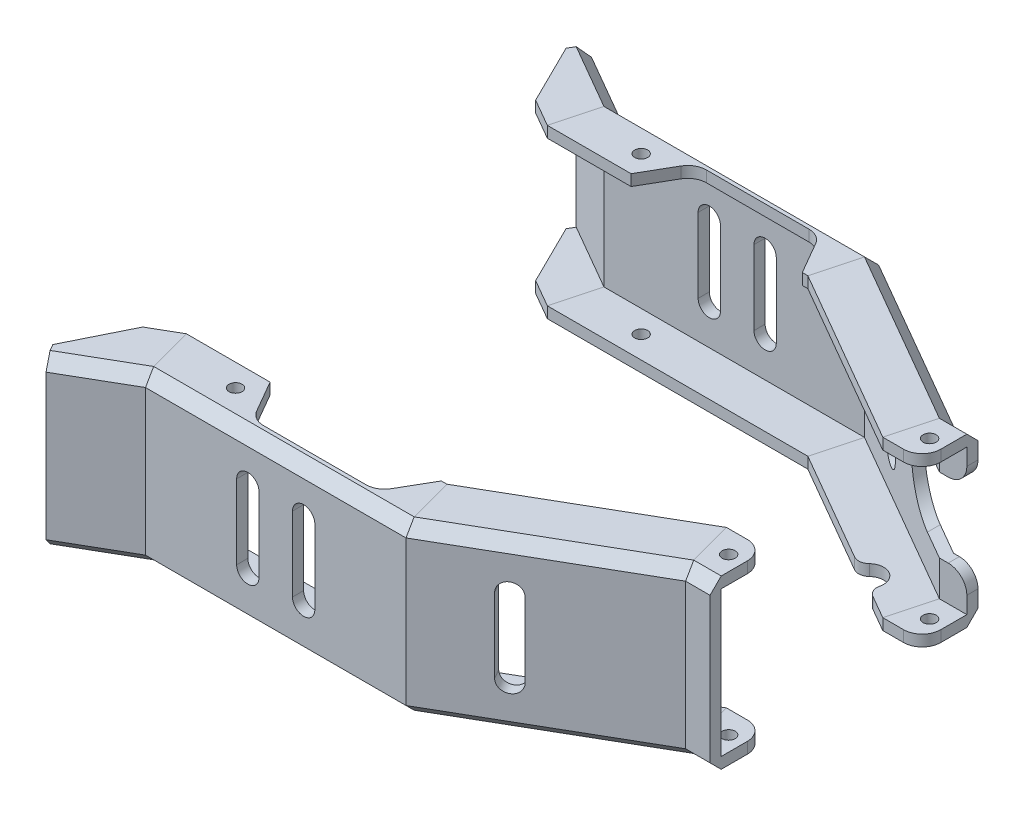
SolidWorks part; units mm, degrees
material "ABS PC"
ref_plane "Front Plane" through (0, 0, 0) normal (0, 0, 1) x (1, 0, 0)
ref_plane "Top Plane" through (0, 0, 0) normal (0, 1, 0) x (1, 0, 0)
ref_plane "Right Plane" through (0, 0, 0) normal (1, 0, 0) x (0, 0, -1)
sketch "Sketch6" plane through (0, 0, 0) normal (0, 1, 0) x (1, 0, 0)
  line L0 (0, 0) -> (-70, 0)
  line L1 (-70, 0) -> (-87.3205, -10)
  line L2 (0, 0) -> (47.6314, 27.5)
  line L3 (47.6314, 27.5) -> (54.6314, 27.5)
  dimension "D1" = 70
  dimension "D2" = 20
  dimension "D3" = 150
  dimension "D4" = 55
  dimension "D5" = 7
ref_plane "Plane5" through (0, 0, 0) normal (1, 0, 0) x (0, 0, -1)
sketch "Sketch7" plane through (0, 0, 0) normal (1, 0, 0) x (0, 0, -1)
  line L0 (1.3929, 0) -> (11.0315, 0) construction
  line L2 (-1.6071, -22.5) -> (-1.6071, 22.5)
  line L4 (1.3929, -19.5) -> (1.3929, 19.5)
  line L5 (-1.6071, -22.5) -> (1.3929, 19.5) construction
  line L6 (-1.6071, 22.5) -> (1.3929, -19.5) construction
  line L7 (13.3929, 19.5) -> (13.3929, 22.5)
  line L8 (1.3929, -19.5) -> (13.3929, -19.5)
  line L10 (-1.6071, -22.5) -> (13.3929, -22.5)
  line L11 (13.3929, -19.5) -> (13.3929, -22.5)
  line L12 (-1.6071, 22.5) -> (13.3929, 22.5)
  line L14 (1.3929, 19.5) -> (13.3929, 19.5)
  point P0 (0, 0)
  dimension "D1" = 3
  dimension "D3" = 3
  dimension "D2" = 39
  dimension "D5" = 15
sweep "Sweep8" add profiles "Sketch7" path "Sketch6"
ref_plane "Plane6" through (0, 0, -61.8929) normal (0, 0, -1) x (-1, 0, 0)
sketch "Sketch8" plane through (0, 22.5, 0) normal (0, 1, 0) x (1, 0, 0)
  line L1 (-73.5886, 13.3929) -> (-94.0169, 1.5986) construction
  line L3 (-89.0169, -7.0617) -> (-94.0169, 1.5986)
  line L4 (-94.0169, 1.5986) -> (-81.0266, 9.0986)
  line L5 (-94.0169, 1.5986) -> (-86.5169, -11.3918) construction
  line L6 (-81.0266, 9.0986) -> (-89.0169, -7.0617)
  dimension "D1" = 15
  dimension "D2" = 10
extrude "Cut-Extrude1" cut sketch "Sketch8" against normal through all
sketch "Sketch10" plane through (0, 22.5, 0) normal (0, 1, 0) x (1, 0, 0)
  line L0 (-3.5886, 13.3929) -> (-73.5886, 13.3929) construction
  line L1 (-51.0886, 13.3929) -> (-5.0886, 13.3929)
  line L5 (-5.0886, 13.3929) -> (-11.4395, 2.3929)
  line L6 (-11.4395, 2.3929) -> (-44.7378, 2.3929)
  line L7 (-28.0886, 2.3929) -> (-28.0886, 13.3929) construction
  line L8 (-51.0886, 13.3929) -> (-44.7378, 2.3929)
  point P6 (-28.0886, 13.3929)
  dimension "D1" = 11
  dimension "D2" = 46
  dimension "D3" = 24.5
  dimension "D4" = 60
extrude "Cut-Extrude3" cut sketch "Sketch10" against normal blind 5
sketch "Sketch11" plane through (0, 0, 1.6071) normal (0, 0, 1) x (1, 0, 0)
  line L0 (-34.5694, 23.5) -> (-34.5694, -22.5) construction
  line L3 (-42.0694, -9.5) -> (-42.0694, 10.5) construction
  line L4 (-45.0694, -9.5) -> (-45.0694, 10.5)
  line L5 (-39.0694, -9.5) -> (-39.0694, 10.5)
  line L6 (-27.0694, -9.5) -> (-27.0694, 10.5) construction
  line L7 (-24.0694, -9.5) -> (-24.0694, 10.5)
  line L8 (-30.0694, -9.5) -> (-30.0694, 10.5)
  line L9 (-34.5694, 0.5) -> (-42.0694, 0.5) construction
  line L11 (0.4306, -22.5) -> (-69.5694, -22.5) construction
  arc A0 (-45.0694, -9.5) -> (-39.0694, -9.5) centre (-42.0694, -9.5) ccw
  arc A1 (-39.0694, 10.5) -> (-45.0694, 10.5) centre (-42.0694, 10.5) ccw
  arc A2 (-24.0694, -9.5) -> (-30.0694, -9.5) centre (-27.0694, -9.5) cw
  arc A3 (-30.0694, 10.5) -> (-24.0694, 10.5) centre (-27.0694, 10.5) cw
  point P8 (-42.0694, 0.5)
  point P15 (-27.0694, 0.5)
  dimension "D1" = 15
  dimension "D2" = 6
  dimension "D3" = 20
  dimension "D4" = 23
extrude "Cut-Extrude4" cut sketch "Sketch11" against normal blind 10
chamfer "Chamfer1" distance 3 angle 45 8 edges at (-78.0432, -22.5, 6.4995) (-34.5694, -22.5, 1.6071) (24.2463, -22.5, -12.1429) (-78.0432, 22.5, 6.4995) (-34.5694, 22.5, 1.6071) (24.2463, 22.5, -12.1429) (51.3467, -22.5, -25.8929) (51.3467, 22.5, -25.8929)
sketch "Sketch14" plane through (0.8036, 0, 1.3918) normal (0.5, 0, 0.866) x (0.866, 0, -0.5)
  line L0 (20, -10) -> (20, 10) construction
  line L1 (17, -10) -> (17, 10)
  line L2 (23, -10) -> (23, 10)
  line L5 (0, 0) -> (20, 0) construction
  arc A0 (17, -10) -> (23, -10) centre (20, -10) ccw
  arc A1 (23, 10) -> (17, 10) centre (20, 10) ccw
  point P2 (20, 0)
  dimension "D1" = 20
  dimension "D2" = 6
  dimension "D3" = 20
extrude "Cut-Extrude6" cut sketch "Sketch14" against normal blind 3
hole_wizard "Ø3.5 (3.5) Diameter Hole1" positions "Sketch18" profile "Sketch19" hole size "Ø3.5" standard "ANSI Metric" end condition through all
sketch "Sketch18" plane through (0, -22.5, 0) normal (0, -1, 0) x (-1, 0, 0)
  line L6 (-50.6314, 34.8929) -> (-50.6314, 28.8929) construction
  line L7 (-54.6314, 28.8929) -> (-47.2582, 28.8929) construction
  line L11 (54.3686, 7.3929) -> (54.3686, 1.3929) construction
  line L12 (0.3732, 1.3929) -> (70.3732, 1.3929) construction
  line L14 (-54.6314, 28.8929) -> (-54.6314, 40.8929) construction
  point P0 (54.3686, 7.3929)
  point P2 (-50.6314, 34.8929)
  dimension "D1" = 6
  dimension "D2" = 105
  dimension "D3" = 4
sketch "Sketch19" plane through (-54.3686, -22.5, -7.3929) normal (1, 0, 0) x (0, 0, -1)
  line L0 (0, 0) -> (0, 45)
  line L1 (0, 45) -> (1.75, 45)
  line L2 (1.75, 45) -> (1.75, 0)
  line L5 (1.75, 0) -> (0, 0)
  line L11 (0, -6.35) -> (0, 107.95) construction
  dimension "Thru Hole Dia." = 3.5
  dimension "Thru Hole Depth" = 45
sketch "Sketch22" plane through (0, -22.5, 0) normal (0, -1, 0) x (1, 0, 0)
  line L0 (28.4543, -31.8929) -> (35.3825, -35.8929)
  line L1 (28.4543, -31.8929) -> (28.9543, -31.0268)
  line L2 (35.3825, -35.8929) -> (35.8825, -35.0268)
  line L3 (28.9543, -31.0268) -> (35.8825, -35.0268)
  line L4 (44.0428, -40.8929) -> (-3.5886, -13.3929) construction
  arc A0 (28.9543, -31.0268) -> (35.8825, -35.0268) centre (32.4184, -33.0268) cw
  point P6 (31.9184, -33.8929)
  line M7 (-3.5886, -13.3929) -> (44.0428, -40.8929)
  dimension "D1" = 1
  dimension "D2" = 8
  dimension "D3" = 14
extrude "Cut-Extrude9" cut sketch "Sketch22" against normal blind 10 contours A0 L3 | L3 L1 L2 M7 region at (32.1684, -22.5, -33.4598) region at (33.2673, -22.5, -31.5566)
mirror "Mirror2" about plane through (0, 0, -61.8929) normal (0, 0, -1) of bodies 116 103
sketch "Sketch20" plane through (0, 0, -97.8929) normal (0, 0, -1) x (-1, 0, 0)
  line L0 (-54.6314, 0) -> (-47.1314, 0) construction
  line L1 (-54.6314, 19.5) -> (-54.6314, -19.5) construction
  line L3 (-39.6314, -10) -> (-54.6314, -10)
  line L4 (-39.6314, -10) -> (-39.6314, 10)
  line L5 (-39.6314, 10) -> (-54.6314, 10)
  line L6 (-54.6314, -10) -> (-54.6314, 10)
  line L7 (-39.6314, -10) -> (-54.6314, 10) construction
  line L8 (-39.6314, 10) -> (-54.6314, -10) construction
  arc A0 (-39.6314, 10) -> (-39.6314, -10) centre (-39.6314, 0) cw
  point P5 (-47.1314, 0)
  line M3 (-48.062, -19.5) -> (-48.062, 19.5)
  line M5 (-54.6314, 19.5) -> (-54.6314, -19.5)
  dimension "D1" = 20
  dimension "D2" = 15
extrude "Cut-Extrude7" cut sketch "Sketch20" against normal blind 5 and the other way through all contours A0 L4 | L5 L3 M3 M5 | L4 L5 L3 M3 region at (43.8467, 0, -97.8929) region at (35.3873, 0, -97.8929) region at (51.3467, 0, -97.8929)
sketch "Sketch21" plane through (0, 0, -25.8929) normal (0, 0, 1) x (1, 0, 0)
  line L0 (54.6314, 0) -> (49.6314, 0) construction
  line L2 (54.6314, 19.5) -> (54.6314, -19.5) construction
  line L3 (54.6314, -7.5) -> (44.6314, -7.5)
  line L4 (54.6314, -7.5) -> (54.6314, 7.5)
  line L5 (54.6314, 7.5) -> (44.6314, 7.5)
  line L6 (44.6314, -7.5) -> (44.6314, 7.5)
  line L7 (54.6314, -7.5) -> (44.6314, 7.5) construction
  line L8 (54.6314, 7.5) -> (44.6314, -7.5) construction
  arc A0 (44.6314, 7.5) -> (44.6314, -7.5) centre (44.6314, 0) ccw
  point P5 (49.6314, 0)
  line M14 (48.062, 19.5) -> (48.062, -19.5)
  line M16 (54.6314, -19.5) -> (54.6314, 19.5)
  dimension "D1" = 15
  dimension "D2" = 10
extrude "Cut-Extrude8" [suppressed] cut sketch "Sketch21" against normal blind 10 and the other way blind 10 contours A0 M14 | L6 A0 M14 | L6 L3 L5 M16
fillet "Fillet1" radius 3 2 edges at (28.4543, -21, -31.8929) (35.3825, -21, -35.8929)
fillet "Fillet2" radius 3 2 edges at (28.4543, -21, -91.8929) (35.3825, -21, -87.8929)
fillet "Fillet3" radius 5 2 edges at (54.6314, 21, -40.8929) (54.6314, -21, -40.8929)
fillet "Fillet4" radius 5 2 edges at (54.6314, 21, -82.8929) (54.6314, -21, -82.8929)
fillet "Fillet5" radius 5 2 edges at (54.6314, 10, -96.3929) (54.6314, -10, -96.3929)
fillet "Fillet6" radius 5 2 edges at (-44.7378, 21, -2.3929) (-11.4395, 21, -2.3929)
fillet "Fillet7" radius 5 2 edges at (-44.7378, 21, -121.3929) (-11.4395, 21, -121.3929)
